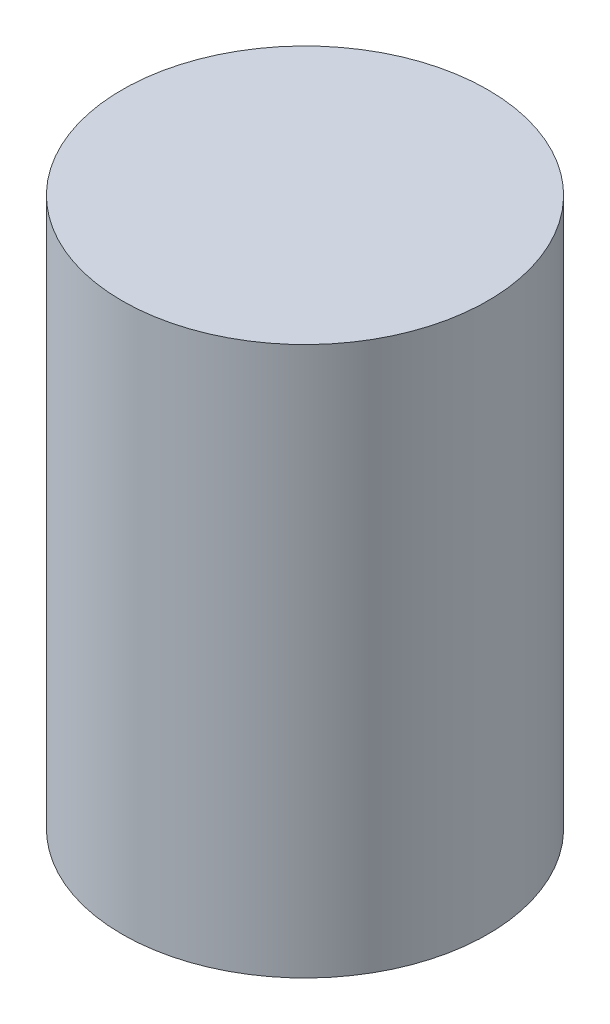
SolidWorks part; units mm, degrees
ref_plane "Front Plane" through (0, 0, 0) normal (0, 0, 1) x (1, 0, 0)
ref_plane "Top Plane" through (0, 0, 0) normal (0, 1, 0) x (1, 0, 0)
ref_plane "Right Plane" through (0, 0, 0) normal (1, 0, 0) x (0, 0, -1)
sketch "Sketch1" plane through (0, 0, 0) normal (0, 1, 0) x (1, 0, 0)
  circle A0 centre (-17.4188, 18.5985) radius 60
extrude "Boss-Extrude1" add sketch "Sketch1" along normal blind 180
ref_point "wrist point"
ref_axis "wrist+front" through (-17.4188, 180, -18.5985) along (0, 0, 1)
ref_axis "wrist+right" through (-17.4188, 180, -18.5985) along (1, 0, 0)
ref_axis "wrist+top" through (-17.4188, 180, -18.5985) along (0, 1, 0)
ref_plane "Plane1" through (-17.4188, 180, -18.5985) normal (0, 1, 0) x (1, 0, 0)
ref_plane "Plane2" through (-17.4188, 210, -18.5985) normal (0, 1, 0) x (1, 0, 0)
ref_point "ball center"
ref_axis "tilt" through (-17.4188, 210, -18.5985) along (1, 0, 0)
